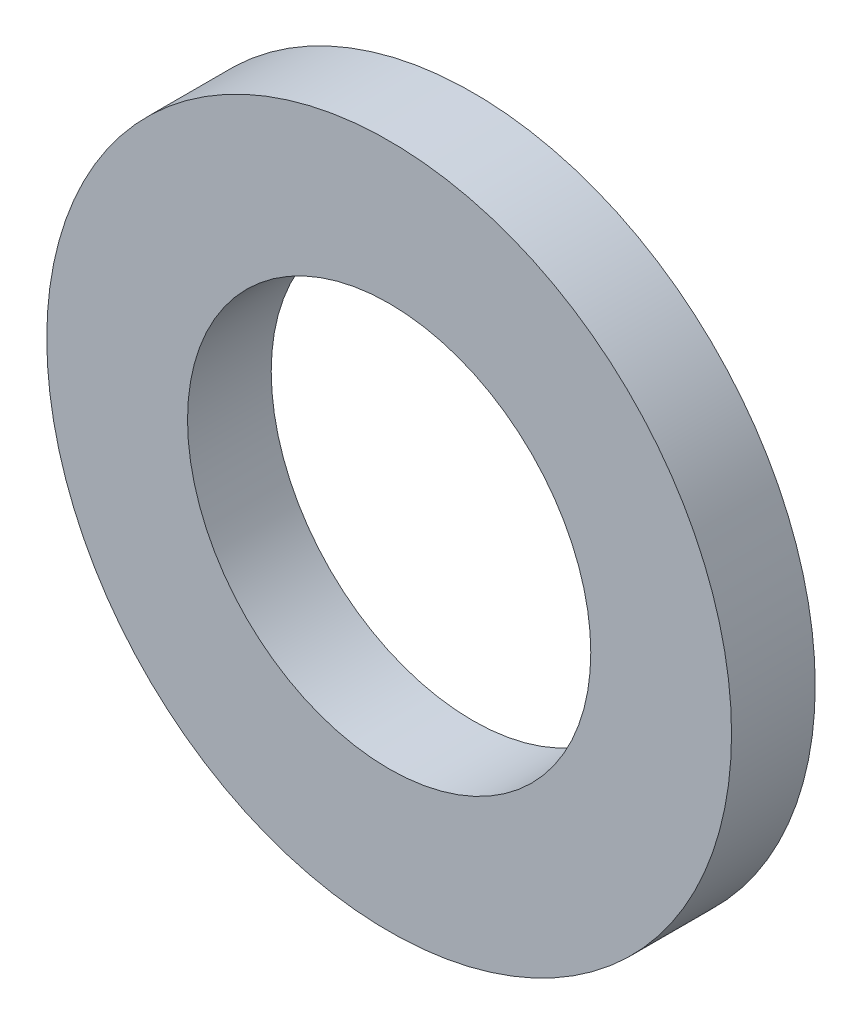
SolidWorks part; units mm, degrees
ref_plane "Front Plane" through (0, 0, 0) normal (0, 0, 1) x (1, 0, 0)
ref_plane "Top Plane" through (0, 0, 0) normal (0, 1, 0) x (1, 0, 0)
ref_plane "Right Plane" through (0, 0, 0) normal (1, 0, 0) x (0, 0, -1)
sketch "Sketch1" plane through (0, 0, 0) normal (0, 0, 1) x (1, 0, 0)
  circle A0 centre (0, 0) radius 4.5
  circle A1 centre (0, 0) radius 2.65
  dimension "OD" = 9
  dimension "ID1" = 5.3
extrude "Boss-Extrude1" add sketch "Sketch1" along normal blind 1.1
ref_axis "Center Axis 1" through (0, 0, 1.1) along (0, 0, -1)
ref_plane "Contact Plane 1" through (0, 0, 1.1) normal (0, 0, 1) x (1, 0, 0)
ref_plane "Contact Plane 2" through (0, 0, 0) normal (0, 0, -1) x (-1, 0, 0)
